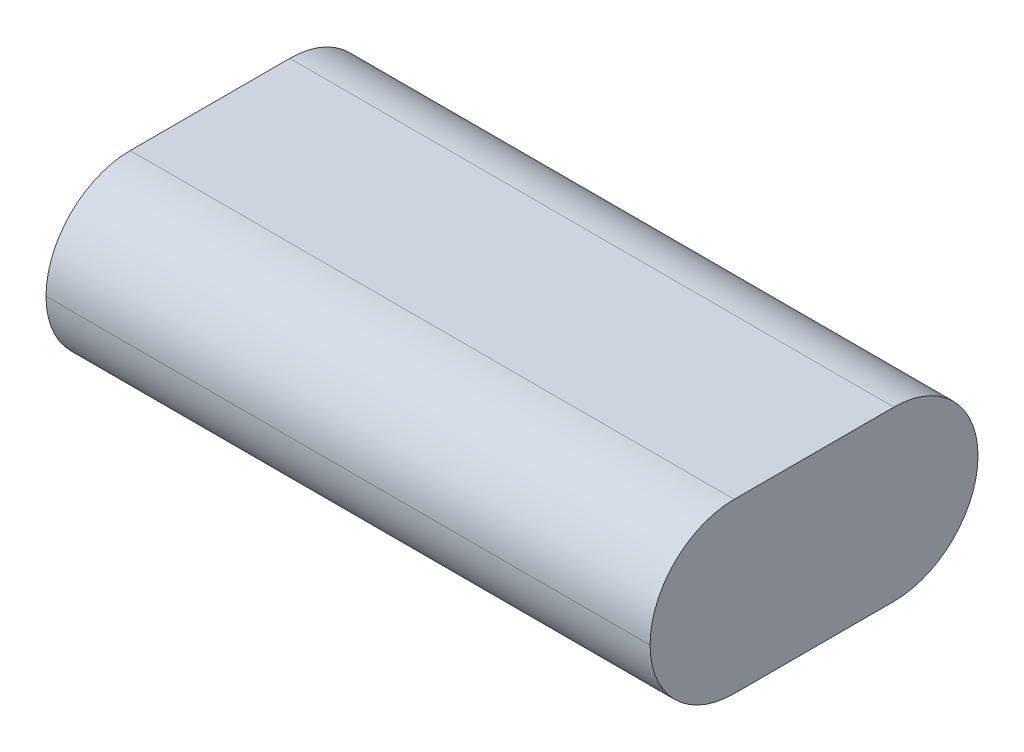
SolidWorks part; units mm, degrees
ref_plane "Front Plane" through (0, 0, 0) normal (0, 0, 1) x (1, 0, 0)
ref_plane "Top Plane" through (0, 0, 0) normal (0, 1, 0) x (1, 0, 0)
ref_plane "Right Plane" through (0, 0, 0) normal (1, 0, 0) x (0, 0, -1)
sketch "Sketch1" plane through (0, 0, 0) normal (0, 1, 0) x (1, 0, 0)
  line L1 (-35, 19) -> (35, 19)
  line L2 (-35, 19) -> (-35, -19)
  line L3 (-35, -19) -> (35, -19)
  line L4 (35, 19) -> (35, -19)
  line L5 (-35, 19) -> (35, -19) construction
  line L6 (-35, -19) -> (35, 19) construction
  point P0 (0, 0)
  dimension "D1" = 70
  dimension "D2" = 38
extrude "Boss-Extrude1" add sketch "Sketch1" along normal blind 19.5
fillet "Fillet1" radius 9.75 4 edges at (0, 0, -19) (0, 0, 19) (0, 19.5, -19) (0, 19.5, 19)
